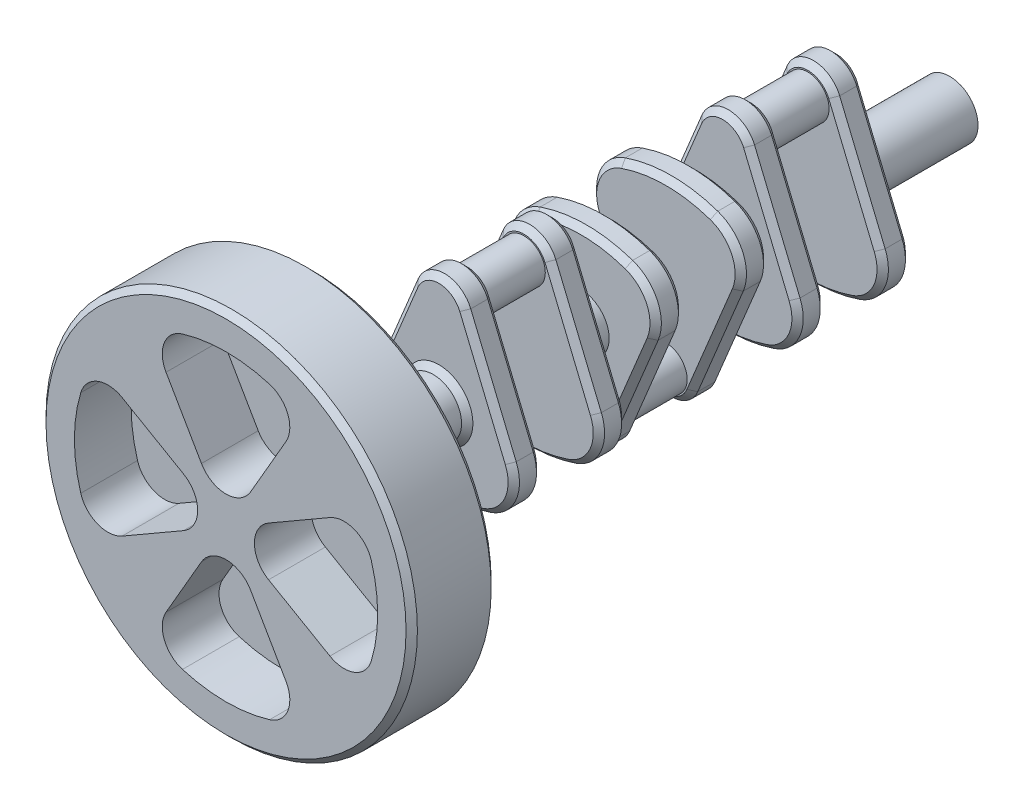
SolidWorks part; units mm, degrees
note: '?' marks a value the reader was unsure of.
material "6061-T6 (SS)"
ref_plane "Front" through (0, 0, 0) normal (0, 0, 1) x (1, 0, 0)
ref_plane "Top" through (0, 0, 0) normal (0, 1, 0) x (1, 0, 0)
ref_plane "Right" through (0, 0, 0) normal (1, 0, 0) x (0, 0, -1)
other "Center of Mass"
sketch "Sketch1" plane through (0, 0, 0) normal (0, 0, 1) x (1, 0, 0)
  circle A1 centre (0, 0) radius 9.525
  dimension "D2" = 19.05
extrude "Boss-Extrude1" add sketch "Sketch1" against normal blind 25.4 contours A1
sketch "Sketch2" plane through (0, 0, -25.4) normal (0, 0, -1) x (-1, 0, 0)
  line L0 (-11.7333, 4.8601) -> (-38.5824, -59.9596)
  line L1 (11.7333, 4.8601) -> (38.5824, -59.9596)
  line L2 (0, 0) -> (0, 30.2986) construction
  arc A0 (11.7333, 4.8601) -> (-11.7333, 4.8601) centre (0, 0) ccw
  arc A1 (-38.5824, -59.9596) -> (38.5824, -59.9596) centre (0, -9.525) ccw
  dimension "D1" = 12.7
  dimension "D2" = 63.5
  dimension "D3" = 45
  dimension "D4" = 9.525
extrude "Boss-Extrude2" add sketch "Sketch2" along normal blind 12.7
fillet "Fillet1" radius 19.05 2 edges at (38.5824, -59.9596, -31.75) (-38.5824, -59.9596, -31.75)
ref_plane "Plane1" through (0, 0, -12.7) normal (0, 0, 1) x (1, 0, 0)
mirror "Mirror2" about plane through (0, 0, -12.7) normal (0, 0, 1) of bodies 102
ref_point "Point1"
sketch "Sketch3" plane through (0, 0, -38.1) normal (0, 0, -1) x (-1, 0, 0)
  circle A0 centre (0, -36.5914) radius 12.7
  point P0 (0, -36.5914)
  dimension "D1" = 25.4
extrude "Boss-Extrude3" add sketch "Sketch3" along normal blind 12.7 separate body
pattern_linear "LPattern1" count 3 spacing 63.5 along (0, 0, -1) of bodies 104
ref_axis "Axis1" through (0, -36.5914, -50.8) along (0, 0, 1)?
move or copy body "Body-Move/Copy1" bodies to move or copy 106 copy no rotation origin (0, -36.5914, 0) rotation axis (0, 0, 1) rotation angle 180
pattern_linear "LPattern2" count 2 spacing 63.5 along (0, 0, -1) of "Boss-Extrude3"
sketch "Sketch4" plane through (0, 0, 12.7) normal (0, 0, 1) x (1, 0, 0)
  circle A0 centre (0, -36.5914) radius 12.7 construction
  circle A1 centre (0, -36.5914) radius 12.7
extrude "Boss-Extrude4" add sketch "Sketch4" along normal blind 57.15
sketch "Sketch5" plane through (0, 0, -165.1) normal (0, 0, -1) x (-1, 0, 0)
  line L2 (-11.7333, 4.8601) -> (-32.0796, -44.2604)
  line L3 (32.0796, -44.2604) -> (11.7333, 4.8601)
  line L4 (-11.7333, 4.8601) -> (-32.0796, -44.2604)
  line L5 (32.0796, -44.2604) -> (11.7333, 4.8601)
  circle A0 centre (0, -36.5914) radius 12.7 construction
  circle A1 centre (0, -36.5914) radius 12.7
  arc A4 (-32.0796, -44.2604) -> (-20.6853, -69.5614) centre (-14.4797, -51.5505) ccw
  arc A5 (-20.6853, -69.5614) -> (20.6853, -69.5614) centre (0, -9.525) ccw
  arc A6 (20.6853, -69.5614) -> (32.0796, -44.2604) centre (14.4797, -51.5505) ccw
  arc A7 (11.7333, 4.8601) -> (-11.7333, 4.8601) centre (0, 0) ccw
  arc A8 (-32.0796, -44.2604) -> (-20.6853, -69.5614) centre (-14.4797, -51.5505) ccw
  arc A9 (-20.6853, -69.5614) -> (20.6853, -69.5614) centre (0, -9.525) ccw
  arc A10 (20.6853, -69.5614) -> (32.0796, -44.2604) centre (14.4797, -51.5505) ccw
  arc A11 (11.7333, 4.8601) -> (-11.7333, 4.8601) centre (0, 0) ccw
  dimension "D1" = 0
extrude "Boss-Extrude5" add sketch "Sketch5" along normal blind 50.8 contours A1
sketch "Sketch6" plane through (0, 0, 69.85) normal (0, 0, 1) x (1, 0, 0)
  circle A0 centre (0, -36.5914) radius 83.1071
extrude "Boss-Extrude6" add sketch "Sketch6" along normal blind 38.1
combine bodies "Combine1" operation type add bodies to combine 105 108 109 111 112
chamfer "Chamfer1" distance 2.54 angle 45 76 edges at (-12.7, -36.5914, -165.1) (12.7, -36.5914, 12.7) (-31.8495, -59.373, -152.4) (-21.9064, -19.7001, -152.4) (0, -73.025, -152.4) (0, 12.7, -152.4) (31.8495, -59.373, -152.4) (21.9064, -19.7001, -152.4) (-31.8495, -59.373, -165.1) (-21.9064, -19.7001, -165.1) (0, -73.025, -165.1) (0, 12.7, -165.1) (31.8495, -59.373, -165.1) (21.9064, -19.7001, -165.1) (-31.8495, -59.373, -127) (-21.9064, -19.7001, -127) (0, -73.025, -127) (0, 12.7, -127) (31.8495, -59.373, -127) (21.9064, -19.7001, -127) (-31.8495, -59.373, -114.3) (-21.9064, -19.7001, -114.3) (0, -73.025, -114.3) (0, 12.7, -114.3) (31.8495, -59.373, -114.3) (21.9064, -19.7001, -114.3) (-21.9064, -53.4827, -101.6) (-31.8495, -13.8098, -101.6) (0, -85.8828, -101.6) (0, -0.1578, -101.6) (21.9064, -53.4827, -101.6) (31.8495, -13.8098, -101.6) (-21.9064, -53.4827, -88.9) (0, -85.8828, -88.9) (-31.8495, -13.8098, -88.9) (21.9064, -53.4827, -88.9) (0, -0.1578, -88.9) (31.8495, -13.8098, -88.9) (-21.9064, -53.4827, -63.5) (0, -85.8828, -63.5) (-31.8495, -13.8098, -63.5) (21.9064, -53.4827, -63.5) (0, -0.1578, -63.5) (31.8495, -13.8098, -63.5) (-21.9064, -53.4827, -50.8) (-31.8495, -13.8098, -50.8) (0, -85.8828, -50.8) (0, -0.1578, -50.8) (21.9064, -53.4827, -50.8) (31.8495, -13.8098, -50.8) (-21.9064, -19.7001, -38.1) (0, 12.7, -38.1) (-31.8495, -59.373, -38.1) (21.9064, -19.7001, -38.1) (0, -73.025, -38.1) (31.8495, -59.373, -38.1) (-21.9064, -19.7001, -25.4) (-31.8495, -59.373, -25.4) (0, 12.7, -25.4) (0, -73.025, -25.4) (21.9064, -19.7001, -25.4) (31.8495, -59.373, -25.4) (-21.9064, -19.7001, 0) (-31.8495, -59.373, 0) (0, 12.7, 0) (0, -73.025, 0) (21.9064, -19.7001, 0) (31.8495, -59.373, 0) (-21.9064, -19.7001, 12.7) (0, 12.7, 12.7) (-31.8495, -59.373, 12.7) (21.9064, -19.7001, 12.7) (0, -73.025, 12.7) (31.8495, -59.373, 12.7) (83.1071, -36.5914, 69.85) (83.1071, -36.5914, 107.95)
ref_plane "Plane2" through (0, 0, 69.85) normal (0, 0, -1) x (-1, 0, 0)
ref_plane "Plane3" through (0, 0, -12.7) normal (0, 0, -1) x (-1, 0, 0)
ref_plane "Plane4" through (0, 0, -76.2) normal (0, 0, 1) x (1, 0, 0)
ref_plane "Plane5" through (0, 0, -139.7) normal (0, 0, 1) x (1, 0, 0)
sketch "Sketch7" plane through (0, 0, -215.9) normal (0, 0, -1) x (-1, 0, 0)
  line L1 (-1.5875, -25.4789) -> (1.5875, -25.4789)
  line L2 (-1.5875, -25.4789) -> (-1.5875, -28.6539)
  line L3 (-1.5875, -28.6539) -> (1.5875, -28.6539)
  line L4 (1.5875, -25.4789) -> (1.5875, -28.6539)
  line L5 (-1.5875, -25.4789) -> (1.5875, -28.6539) construction
  line L6 (-1.5875, -28.6539) -> (1.5875, -25.4789) construction
  circle A0 centre (0, -36.5914) radius 9.525
  point P3 (0, -27.0664)
  dimension "D1" = 19.05
  dimension "D2" = 3.175
extrude "Cut-Extrude1" cut sketch "Sketch7" against normal blind 25.4 contours A0 L4 L1 L2 | L4 A0 L2 L3 | L2 A0 L4 L3
pattern_circular "CirPattern1" count 4 over 360 about axis through (0, -36.5914, 0) along (0, 0, 1) of "Cut-Extrude1"
sketch "Sketch8" plane through (0, 0, 107.95) normal (0, 0, 1) x (1, 0, 0)
  line L0 (-10.9985, -17.5414) -> (-33.9335, 22.1832)
  line L1 (10.9985, -17.5414) -> (33.9335, 22.1832)
  line L2 (0, 31.2757) -> (0, -36.5914) construction
  arc A0 (-33.9335, 22.1832) -> (33.9335, 22.1832) centre (0, -36.5914) cw
  circle A1 centre (0, -36.5914) radius 80.5671 construction
  arc A2 (10.9985, -17.5414) -> (-10.9985, -17.5414) centre (0, -11.1914) cw
  dimension "D1" = 12.7
  dimension "D3" = 12.7
  dimension "D2" = 60
extrude "Cut-Extrude2" cut sketch "Sketch8" against normal blind 25.4
fillet "Fillet2" radius 12.7 2 edges at (-33.9335, 22.1832, 95.25) (33.9335, 22.1832, 95.25)
pattern_circular "CirPattern5" count 4 over 360 about axis through (0, -36.5914, 0) along (0, 0, 1) of "Cut-Extrude2", "Fillet2"
